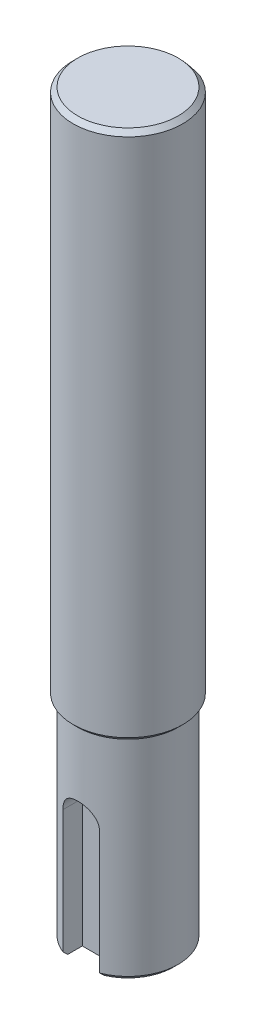
SolidWorks part; units mm, degrees
ref_plane "Piano frontale" through (0, 0, 0) normal (0, 0, 1) x (1, 0, 0)
ref_plane "Piano superiore" through (0, 0, 0) normal (0, 1, 0) x (1, 0, 0)
ref_plane "Piano destro" through (0, 0, 0) normal (1, 0, 0) x (0, 0, -1)
sketch "Schizzo1" plane through (0, 0, 0) normal (0, 1, 0) x (1, 0, 0)
  circle A0 centre (0, 0) radius 6
  dimension "D1" = 12
extrude "Estrusione-Estrusione1" add sketch "Schizzo1" along normal blind 58
sketch "Schizzo2" plane through (0, 0, 0) normal (0, -1, 0) x (1, 0, 0)
  circle A0 centre (0, 0) radius 5.5
  dimension "D1" = 11
extrude "Estrusione-Estrusione2" add sketch "Schizzo2" along normal blind 23
sketch "Schizzo3" plane through (0, 0, 0) normal (0, 0, 1) x (1, 0, 0)
  line L0 (6, 58) -> (-6, 58) construction
  line L1 (-2.5, 58) -> (2.5, 58)
  line L2 (-2.5, 58) -> (-2.5, 53)
  line L3 (-2.5, 53) -> (2.5, 53)
  line L4 (2.5, 58) -> (2.5, 53)
  line L5 (0, 58) -> (0, -23) construction
  line L6 (-5.5, -23) -> (5.5, -23) construction
  dimension "D1" = 5
  dimension "D2" = 5
extrude "Taglio-Estrusione1" cut sketch "Schizzo3" against normal blind 5 from offset 5.5 offset against normal yes
ref_plane "Piano1" through (0, 0, 5.5) normal (0, 0, 1) x (1, 0, 0)
sketch "Schizzo5" plane through (0, 0, 5.5) normal (0, 0, 1) x (1, 0, 0)
  line L0 (0, -23) -> (0, -9) construction
  line L1 (-5.5, -23) -> (5.5, -23) construction
  line L2 (-2, -23) -> (-2, -9)
  line L3 (2, -23) -> (2, -9)
  arc A0 (-2, -23) -> (2, -23) centre (0, -23) ccw
  arc A1 (2, -9) -> (-2, -9) centre (0, -9) ccw
  point P5 (0, -16)
  dimension "D1" = 4
  dimension "D2" = 14
extrude "Taglio-Estrusione2" cut sketch "Schizzo5" against normal blind 2.5
chamfer "Smusso1" distance 0.5 angle 45 3 edges at (0, 0, 6) (0, 58, 6) (0, -23, -5.5)
